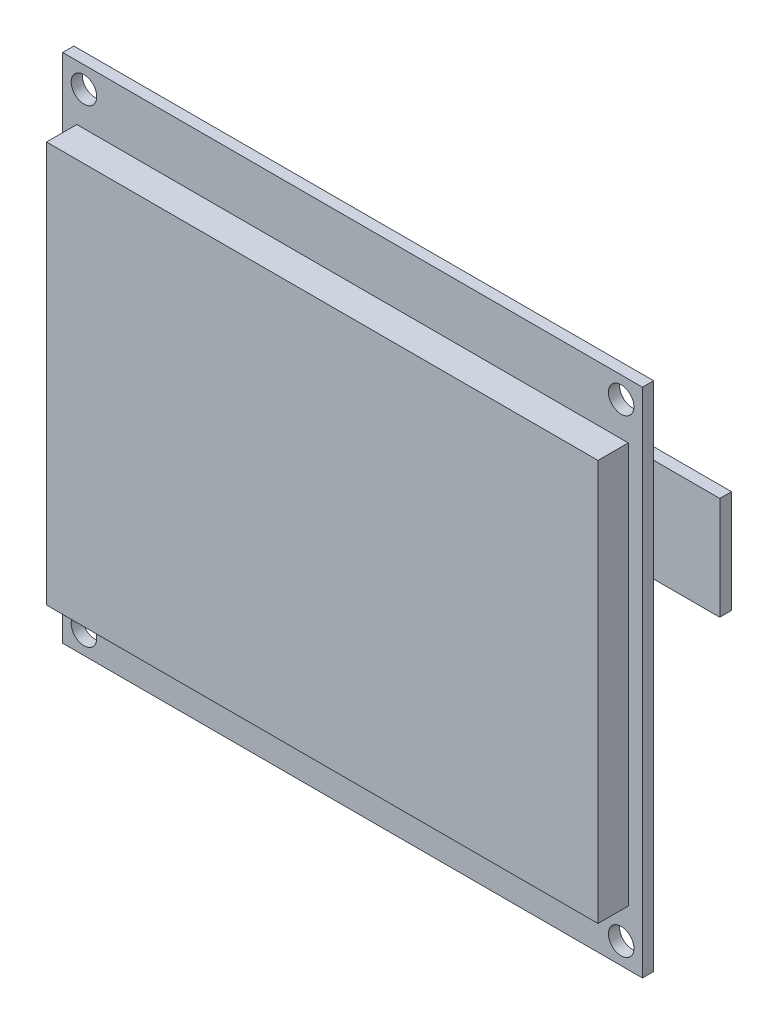
SolidWorks part; units mm, degrees
ref_plane "Front Plane" through (0, 0, 0) normal (0, 0, 1) x (1, 0, 0)
ref_plane "Top Plane" through (0, 0, 0) normal (0, 1, 0) x (1, 0, 0)
ref_plane "Right Plane" through (0, 0, 0) normal (1, 0, 0) x (0, 0, -1)
sketch "Sketch1" plane through (0, 0, 0) normal (0, 0, -1) x (-1, 0, 0)
  line L0 (43.6932, -0.25) -> (41.7, -0.25) construction
  line L1 (-32.25, -24.25) -> (32.25, -24.25) construction
  line L2 (-32.25, -24.25) -> (-32.25, 24.25) construction
  line L3 (-32.25, 24.25) -> (32.25, 24.25) construction
  line L4 (32.25, -24.25) -> (32.25, 24.25) construction
  line L5 (-32.25, -24.25) -> (32.25, 24.25) construction
  line L6 (-32.25, 24.25) -> (32.25, -24.25) construction
  line L7 (-36, 28) -> (41.7, 28) construction
  line L8 (-36, 28) -> (-36, -28.5) construction
  line L9 (-36, -28.5) -> (41.7, -28.5) construction
  line L10 (41.7, 28) -> (41.7, -28.5) construction
  line L11 (-37.9932, 35.7926) -> (43.6932, 35.7926)
  line L12 (-37.9932, 35.7926) -> (-37.9932, -36.2926)
  line L13 (-37.9932, -36.2926) -> (43.6932, -36.2926)
  line L14 (43.6932, 35.7926) -> (43.6932, -36.2926)
  line L15 (2.85, -28.5) -> (2.85, -36.2926) construction
  point P0 (0, 0)
  dimension "D1" = 64.5
  dimension "D2" = 48.5
  dimension "D3" = 3.75
  dimension "D4" = 3.75
  dimension "D5" = 56.5
  dimension "D6" = 77.7
  dimension "D8" = 72.0852
  dimension "D9" = 81.6864
extrude "Boss-Extrude1" add sketch "Sketch1" along normal blind 1.5748
sketch "Sketch2" plane through (0, 0, 0) normal (0, 0, -1) x (-1, 0, 0)
  line L1 (-36, -28.5) -> (41.7, -28.5)
  line L2 (-36, -28.5) -> (-36, 28)
  line L3 (-36, 28) -> (41.7, 28)
  line L4 (41.7, -28.5) -> (41.7, 28)
  line L5 (41.7, 28) -> (49.6841, 28) construction
  line L6 (-36, 28) -> (-43.9841, 28) construction
  line L10 (-32.25, -24.25) -> (32.25, -24.25) construction
  line L11 (-32.25, -24.25) -> (-32.25, 24.25) construction
  line L12 (-32.25, 24.25) -> (32.25, 24.25) construction
  line L13 (32.25, -24.25) -> (32.25, 24.25) construction
  line L14 (-32.25, -24.25) -> (32.25, 24.25) construction
  line L15 (-32.25, 24.25) -> (32.25, -24.25) construction
  point P0 (0, 0)
  point P14 (0, 0)
  dimension "D1" = 56.5
  dimension "D2" = 77.7
  dimension "D3" = 3.75
  dimension "D4" = 48.5
  dimension "D5" = 64.5
  dimension "D6" = 3.75
extrude "Boss-Extrude2" add sketch "Sketch2" against normal blind 4.27
sketch "Sketch3" plane through (0, 0, -1.5748) normal (0, 0, 1) x (1, 0, 0)
  line L0 (37.9932, 35.7926) -> (37.9932, -36.2926) construction
  line L1 (47.3132, 26.0941) -> (17.3132, 26.0941)
  line L2 (47.3132, 26.0941) -> (47.3132, 11.5941)
  line L3 (47.3132, 11.5941) -> (17.3132, 11.5941)
  line L4 (17.3132, 26.0941) -> (17.3132, 11.5941)
  dimension "D1" = 14.5
  dimension "D2" = 30
  dimension "D3" = 9.32
extrude "Boss-Extrude3" add sketch "Sketch3" against normal blind 1.65
sketch "Sketch4" plane through (0, 0, -1.5748) normal (0, 0, -1) x (-1, 0, 0)
  line L0 (43.6932, 35.7926) -> (-37.9932, 35.7926) construction
  line L1 (-37.9932, 35.7926) -> (-37.9932, 26.0941) construction
  line L2 (43.6932, -36.2926) -> (43.6932, 35.7926) construction
  line L3 (-37.9932, -36.2926) -> (43.6932, -36.2926) construction
  circle A0 centre (40.6932, 32.7926) radius 1.8
  circle A1 centre (40.6932, -33.2926) radius 1.8
  circle A2 centre (-34.9932, -33.2926) radius 1.8
  circle A3 centre (-34.9932, 32.7926) radius 1.8
  point P12 (0, 0)
  dimension "D3" = 3.6
  dimension "D1" = 3
  dimension "D2" = 3
  dimension "D4" = 3
  dimension "D5" = 3
extrude "Cut-Extrude1" cut sketch "Sketch4" against normal through all
